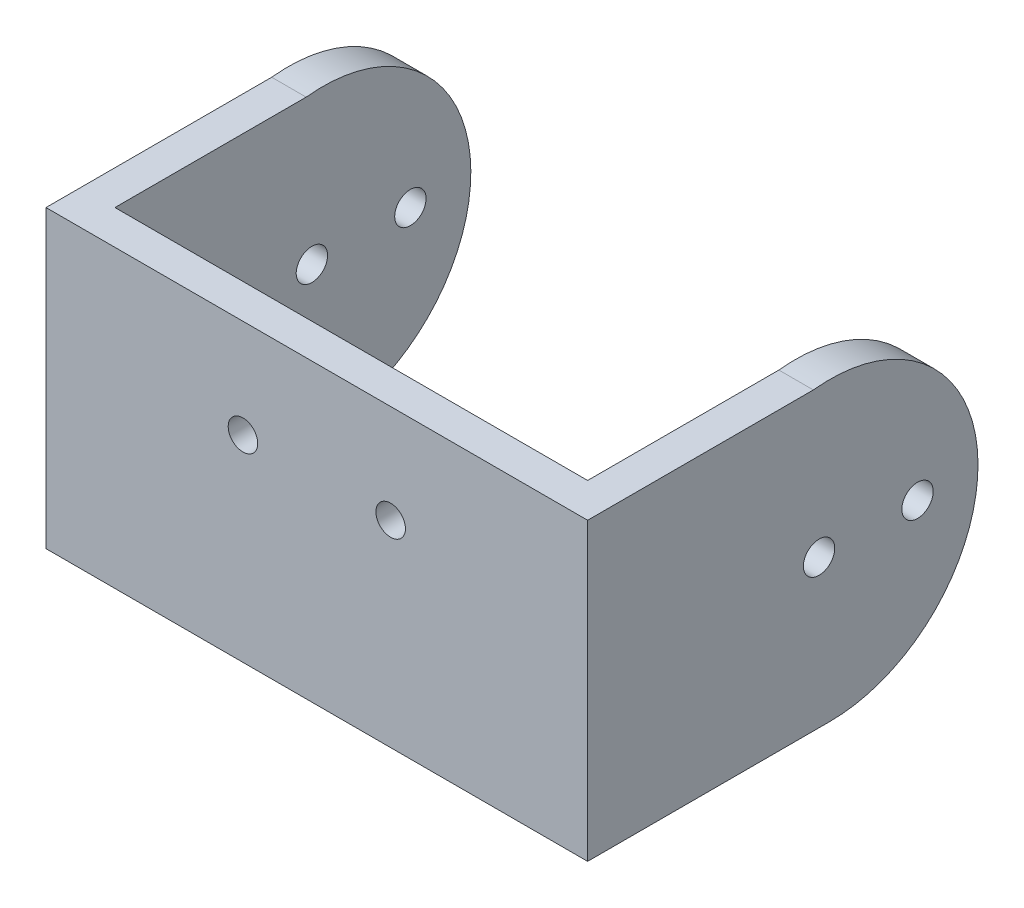
SolidWorks part; units mm, degrees
ref_plane "前视基准面" through (0, 0, 0) normal (0, 0, 1) x (1, 0, 0)
ref_plane "上视基准面" through (0, 0, 0) normal (0, 1, 0) x (1, 0, 0)
ref_plane "右视基准面" through (0, 0, 0) normal (1, 0, 0) x (0, 0, -1)
sketch "草图1" plane through (0, 0, 0) normal (0, 0, 1) x (1, 0, 0)
  line L0 (-33.0551, 0) -> (35.9054, 0) construction
  line L1 (27.5, -15) -> (-27.5, -15)
  line L2 (27.5, -15) -> (27.5, 15)
  line L3 (27.5, 15) -> (-27.5, 15)
  line L4 (-27.5, -15) -> (-27.5, 15)
  line L5 (27.5, -15) -> (-27.5, 15) construction
  line L6 (27.5, 15) -> (-27.5, -15) construction
  line L7 (0, 20.0988) -> (0, -17.0719) construction
  point P0 (0, 0)
  dimension "D1" = 30
  dimension "D2" = 55
extrude "凸台-拉伸1" add sketch "草图1" along normal blind 3.5
ref_plane "基准面1" through (27.5, 0, 0) normal (1, 0, 0) x (0, 0, -1)
sketch "草图2" plane through (27.5, 0, 0) normal (1, 0, 0) x (0, 0, -1)
  line L0 (0, 15) -> (0, -15)
  line L1 (0, -15) -> (0, 15) construction
  line L2 (0, -15) -> (21, -15)
  line L4 (19.4198, 15) -> (0, 15)
  arc A0 (19.4198, 15) -> (21, -15) centre (21.093, 0.0465) cw
  circle A2 centre (20, 0) radius 1.5927
  circle A3 centre (20, 0) radius 10 construction
  circle A15 centre (30, 0) radius 1.5927
  dimension "D7" = 20
extrude "凸台-拉伸2" add sketch "草图2" against normal blind 3.5
mirror "镜向1" about plane through (0, 0, 0) normal (1, 0, 0) of "凸台-拉伸2"
sketch "草图3" plane through (0, 0, 3.5) normal (0, 0, 1) x (1, 0, 0)
  line L0 (0, 15) -> (0, -15) construction
  line L1 (27.5, 15) -> (-27.5, 15) construction
  line L2 (-27.5, -15) -> (27.5, -15) construction
  circle A0 centre (7.5, 5) radius 1.5
  circle A1 centre (-7.5, 5) radius 1.5
  point P12 (27.5, -15)
  dimension "D1" = 15
  dimension "D2" = 3
  dimension "D3" = 20
extrude "切除-拉伸1" cut sketch "草图3" against normal through all
